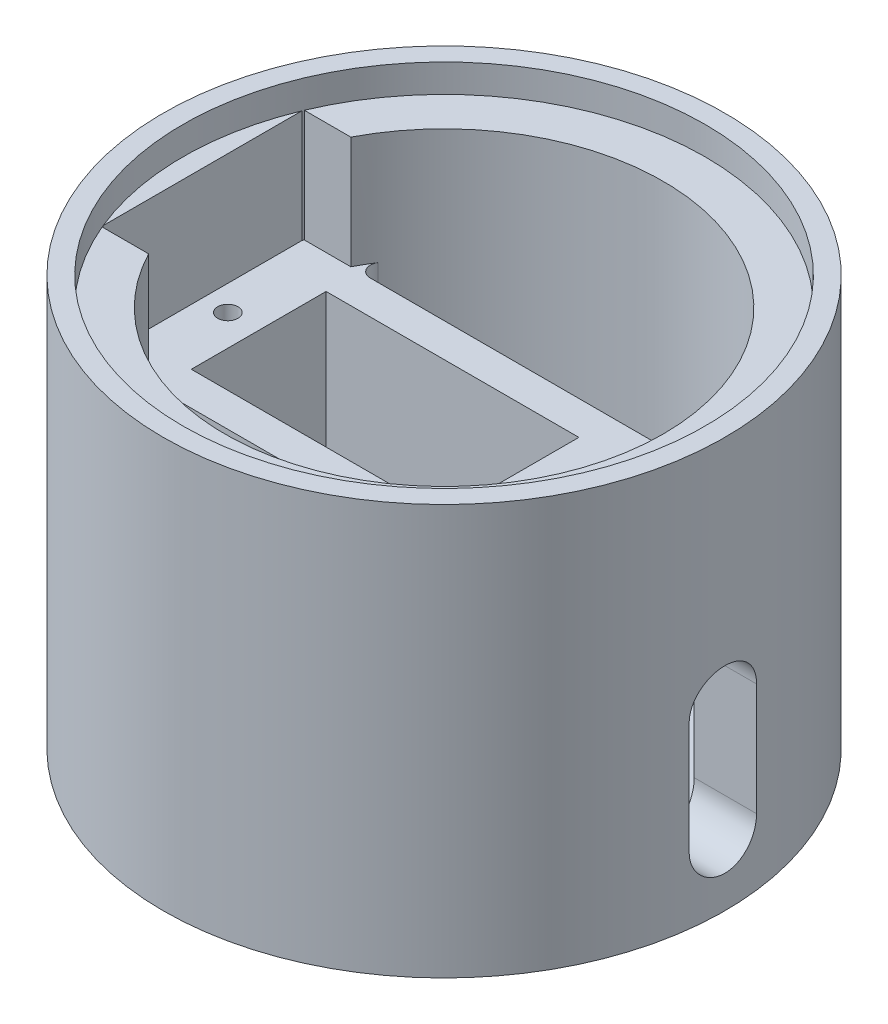
SolidWorks part; units mm, degrees
material "ABS"
ref_plane "前视基准面" through (0, 0, 0) normal (0, 0, 1) x (1, 0, 0)
ref_plane "上视基准面" through (0, 0, 0) normal (0, 1, 0) x (1, 0, 0)
ref_plane "右视基准面" through (0, 0, 0) normal (1, 0, 0) x (0, 0, -1)
sketch "草图1" plane through (0, 0, 0) normal (0, 1, 0) x (1, 0, 0)
  circle A0 centre (0, 0) radius 25
  dimension "D1" = 50
extrude "凸台-拉伸1" add sketch "草图1" along normal blind 3
sketch "草图2" plane through (0, 3, 0) normal (0, 1, 0) x (1, 0, 0)
  line L1 (6, 6) -> (-16.5, 6)
  line L2 (6, 6) -> (6, -6)
  line L3 (6, -6) -> (-16.5, -6)
  line L4 (-16.5, 6) -> (-16.5, -6)
  line L5 (-21.5, 9) -> (11, 9)
  line L6 (-21.5, 9) -> (-21.5, -9)
  line L7 (-21.5, -9) -> (11, -9)
  line L8 (11, 9) -> (11, -9)
  circle A0 centre (0, 0) radius 25
  point P4 (6, 0)
  dimension "D1" = 16.5
  dimension "D2" = 22.5
  dimension "D3" = 12
  dimension "D4" = 5
  dimension "D5" = 3
  dimension "D6" = 5
  dimension "D7" = 3
extrude "凸台-拉伸2" add sketch "草图2" along normal blind 21 contours L8 L5 L6 L7 L4 L1 L2 L3 region at (-5.25, 3, -8.6285)
sketch "草图3" plane through (0, 3, 0) normal (0, 1, 0) x (1, 0, 0)
  line L0 (-17.2988, 9) -> (-21.5, 9)
  line L1 (-21.5, 9) -> (11, 9) construction
  line L2 (-17.2988, -9) -> (-21.5, -9)
  line L3 (-21.5, -9) -> (11, -9) construction
  line L4 (-21.5, 9) -> (-21.5, -9)
  arc A0 (-23.3238, -9) -> (-23.3238, 9) centre (0, 0) ccw
  arc A1 (-17.2988, -9) -> (-17.2988, 9) centre (0, 0) ccw
  arc A2 (-23.3238, -9) -> (-23.3238, 9) centre (0, 0) cw
  dimension "D1" = 50
  dimension "D2" = 39
extrude "凸台-拉伸7" add sketch "草图3" along normal blind 31
fillet "圆角4" radius 1 8 edges at (-3.1494, 3, 9) (-3.1494, 3, -9) (11, 13.5, 9) (11, 24, 0) (11, 13.5, -9) (11, 3, 0) (-17.2988, 13.5, -9) (-17.2988, 13.5, 9)
fillet "圆角5" radius 1 3 edges at (-16.2715, 3.2929, -9.2929) (-16.2715, 3.2929, 9.2929) (19.5, 3, 0)
sketch "草图4" plane through (0, 3, 0) normal (0, 1, 0) x (1, 0, 0)
  circle A0 centre (0, 0) radius 25
  circle A1 centre (0, 0) radius 23.25
  dimension "D1" = 46.5
  dimension "D2" = 50
extrude "凸台-拉伸8" add sketch "草图4" along normal blind 33.5
sketch "草图5" plane through (0, 24, 0) normal (0, 1, 0) x (1, 0, 0)
  line L0 (-5.25, 6) -> (-5.25, 2.058) construction
  line L1 (6, 6) -> (-16.5, 6) construction
  circle A0 centre (-19.25, 0) radius 0.9
  circle A1 centre (8.75, 0) radius 0.9
  dimension "D1" = 14
  dimension "D3" = 1.8
  dimension "D2" = 6
extrude "切除-拉伸1" cut sketch "草图5" against normal blind 5
sketch "草图6" plane through (6, 0, 0) normal (-1, 0, 0) x (0, 0, 1)
  line L0 (0, 5.9) -> (0, 15.9) construction
  line L1 (-3, 5.9) -> (-3, 15.9)
  line L2 (3, 5.9) -> (3, 15.9)
  arc A0 (-3, 5.9) -> (3, 5.9) centre (0, 5.9) ccw
  arc A1 (3, 15.9) -> (-3, 15.9) centre (0, 15.9) ccw
  point P3 (0, 10.9)
  dimension "D1" = 3
  dimension "D2" = 5.9
  dimension "D3" = 10
extrude "切除-拉伸7" cut sketch "草图6" against normal up to surface (18.8193 mm away) up to face at (0, 0, 25)
sketch "草图9" plane through (0, 3, 0) normal (0, 1, 0) x (1, 0, 0)
  line L0 (0, 0) -> (-6.657, 0) construction
  circle A0 centre (0, 13) radius 1.5
  circle A1 centre (0, -13) radius 1.5
  dimension "D2" = 3
  dimension "D1" = 13
extrude "切除-拉伸8" cut sketch "草图9" against normal up to surface (3 mm away) up to face at (0, 0, 25)
